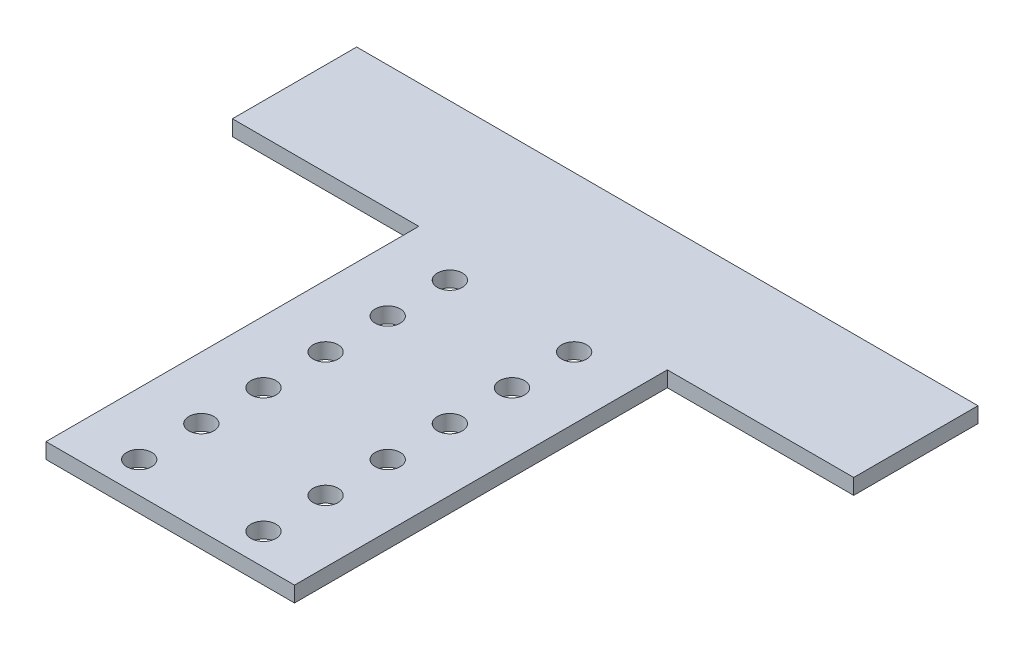
SolidWorks part; units mm, degrees
ref_plane "Front Plane" through (0, 0, 0) normal (0, 0, 1) x (1, 0, 0)
ref_plane "Top Plane" through (0, 0, 0) normal (0, 1, 0) x (1, 0, 0)
ref_plane "Right Plane" through (0, 0, 0) normal (1, 0, 0) x (0, 0, -1)
sketch "Sketch1" plane through (0, 0, 0) normal (0, 1, 0) x (1, 0, 0)
  line L0 (0, 0) -> (50.8, 0)
  line L1 (50.8, 0) -> (50.8, 76.2)
  line L2 (50.8, 76.2) -> (88.9, 76.2)
  line L3 (88.9, 76.2) -> (88.9, 101.6)
  line L4 (88.9, 101.6) -> (-38.1, 101.6)
  line L5 (-38.1, 101.6) -> (-38.1, 76.2)
  line L6 (-38.1, 76.2) -> (0, 76.2)
  line L7 (0, 76.2) -> (0, 0)
  dimension "D1" = 101.6
  dimension "D2" = 76.2
  dimension "D3" = 76.2
  dimension "D4" = 50.8
  dimension "D5" = 127
extrude "Boss-Extrude1" add sketch "Sketch1" along normal blind 3.175
sketch "Sketch2" plane through (0, 3.175, 0) normal (0, 1, 0) x (1, 0, 0)
  line L0 (0, 0) -> (50.8, 0) construction
  line L1 (0, 76.2) -> (0, 0) construction
  line L2 (38.1, 6.35) -> (38.1, 19.05) construction
  circle A0 centre (38.1, 6.35) radius 2.5527
  circle A1 centre (12.7, 6.35) radius 2.5527
  circle A2 centre (38.1, 19.05) radius 2.5527
  circle A3 centre (12.7, 19.05) radius 2.5527
  circle A4 centre (38.1, 31.75) radius 2.5527
  circle A5 centre (12.7, 31.75) radius 2.5527
  circle A6 centre (38.1, 44.45) radius 2.5527
  circle A7 centre (12.7, 44.45) radius 2.5527
  circle A8 centre (38.1, 57.15) radius 2.5527
  circle A9 centre (12.7, 57.15) radius 2.5527
  circle A10 centre (38.1, 69.85) radius 2.5527
  circle A11 centre (12.7, 69.85) radius 2.5527
  dimension "D1" = 6.35
  dimension "D2" = 6.35
  dimension "D3" = 5.1054
  dimension "D4" = 5.1054
  dimension "D5" = 25.4
  dimension "D6" = 12.7
  dimension "D7" = 12.7
extrude "Cut-Extrude1" cut sketch "Sketch2" against normal through all
